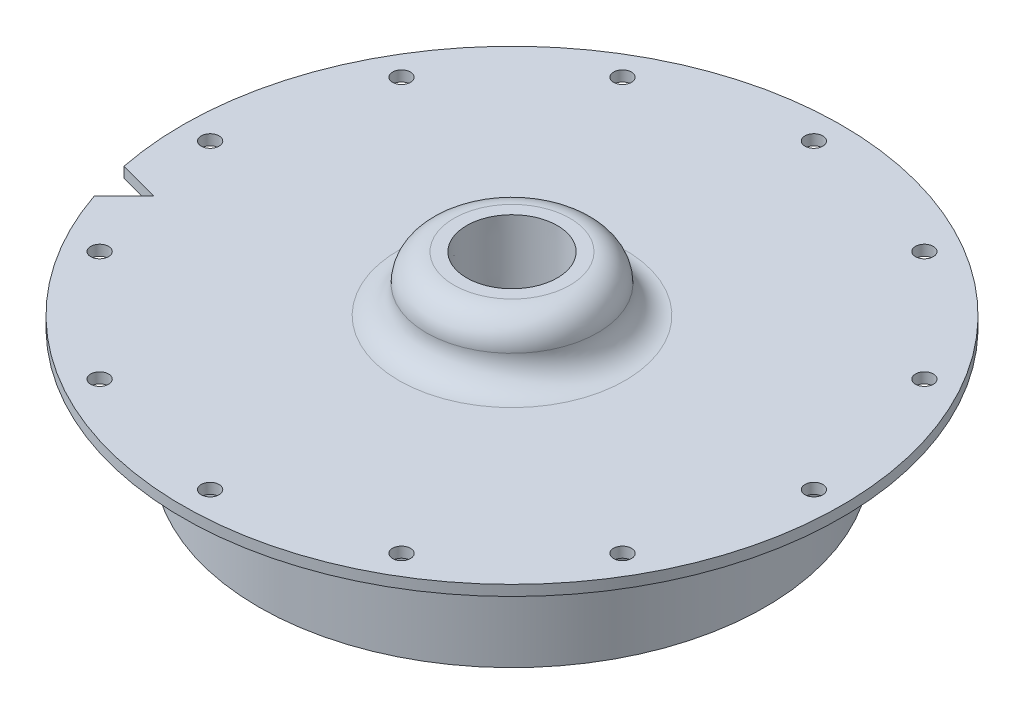
SolidWorks part; units mm, degrees
material "6063-T6"
ref_plane "Front Plane" through (0, 0, 0) normal (0, 0, 1) x (1, 0, 0)
ref_plane "Top Plane" through (0, 0, 0) normal (0, 1, 0) x (1, 0, 0)
ref_plane "Right Plane" through (0, 0, 0) normal (1, 0, 0) x (0, 0, -1)
ref_axis "Axis1" through (0, 55, 0) along (0, -1, 0)
sketch "Sketch1" plane through (0, 0, 0) normal (0, 0, 1) x (1, 0, 0)
  line L0 (-49.784, 0) -> (-39.8399, 0)
  line L1 (0, 55) -> (0, -55) construction
  line L2 (-49.784, 0) -> (-49.784, 1.5875)
  line L3 (-5.588, 9.906) -> (-8.763, 9.906)
  line L5 (-5.588, 9.906) -> (-5.588, 0)
  line L6 (-5.588, 0) -> (0, 0) construction
  line L7 (-49.784, 0) -> (-49.784, 1.5875) construction
  line L8 (-5.588, 1.5875) -> (-5.588, 0) construction
  line L9 (-38.2524, -1.5875) -> (-38.2524, -17.4625)
  line L10 (-38.2524, -17.4625) -> (-35.0774, -17.4625)
  line L11 (-35.0774, -17.4625) -> (-35.0774, -3.175)
  line L12 (-31.9024, 0) -> (-5.588, 0)
  line L13 (0, -201000) -> (0, 249000) construction
  line L14 (-49.784, 1.5875) -> (-17.0815, 1.5875)
  arc A0 (-35.0774, -3.175) -> (-31.9024, 0) centre (-31.9024, -3.175) cw
  arc A1 (-38.2524, -1.5875) -> (-39.8399, 0) centre (-39.8399, -1.5875) ccw
  arc A2 (-17.0815, 1.5875) -> (-12.9223, 5.7467) centre (-17.0815, 5.7467) ccw
  arc A3 (-8.763, 9.906) -> (-12.9223, 5.7467) centre (-8.763, 5.7467) ccw
  point P18 (-35.0774, 0)
  point P25 (0, 0)
  point P28 (-15.0934, 1.8081)
  point P29 (0, 0)
  dimension "D4" = 3.175
  dimension "D5" = 1.5875
  dimension "D1" = 3.175
  dimension "D2" = 38.2524
  dimension "D3" = 17.4625
  dimension "D6" = 1.5875
  dimension "D7" = 3.175
  dimension "D8" = 9.906
revolve "Revolve1" add sketch "Sketch1" angle 360 about axis through (0, 55, 0) along (0, -1, 0)
ref_plane "Hole Location Plane" through (0, 3.175, 0) normal (0, 1, 0) x (1, 0, 0)
sketch "Hole Location" plane through (0, 3.175, 0) normal (0, 1, 0) x (1, 0, 0)
  line L0 (0, 0) -> (-45.6057, 0) construction
  circle A0 centre (0, 0) radius 45.6057 construction
  dimension "D1" = 91.2114
hole_wizard "#36 (0.1065) Diameter Hole1" positions "Sketch2" profile "Sketch3" hole size "#36" standard "ANSI Inch" end condition through all
sketch "Sketch2" plane through (0, 1.5875, 0) normal (0, 1, 0) x (1, 0, 0)
  point P0 (-45.6057, 0)
sketch "Sketch3" plane through (-45.6057, 1.5875, 0) normal (1, 0, 0) x (0, 0, 1)
  line L0 (0, 0) -> (0, 19.05)
  line L1 (0, 19.05) -> (1.3525, 19.05)
  line L2 (1.3525, 19.05) -> (1.3525, 0)
  line L5 (1.3525, 0) -> (0, 0)
  line L11 (0, -6.35) -> (0, 107.95) construction
  dimension "Thru Hole Dia." = 2.7051
  dimension "Thru Hole Depth" = 19.05
pattern_circular "CirPattern1" count 12 over 360 of "#36 (0.1065) Diameter Hole1"
hole_wizard "1/4 NPT Tapped Hole1" positions "Sketch4" profile "Sketch5" size "1/4" standard "ANSI Inch" end condition through all
sketch "Sketch4" plane through (0, 9.906, 0) normal (0, 1, 0) x (1, 0, 0)
  point P0 (0, 0)
sketch "Sketch5" plane through (0, 9.906, 0) normal (1, 0, 0) x (0, 0, 1)
  line L0 (0, 0) -> (0, 27.3685)
  line L1 (0, 27.3685) -> (5.5626, 27.3685)
  line L2 (-6.558, 9.906) -> (-6.8546, 0) construction
  line L3 (5.5626, 27.3685) -> (5.5626, 9.906)
  line L4 (5.5626, 9.906) -> (6.558, 9.906)
  line L5 (6.558, 9.906) -> (6.8546, 0)
  line L7 (6.8546, 0) -> (0, 0)
  line L8 (0, -6.35) -> (0, 107.95) construction
  line L11 (-5.5626, 9.906) -> (-6.558, 9.906) construction
  dimension "Thru Tap Drill Dia." = 11.1252
  dimension "Thru Tap Drill Depth" = 27.3685
  dimension "Thread Dia." = 13.7092
  dimension "Thread Angle" = 3.43
  dimension "Thread Depth" = 9.906
sketch "Sketch6" plane through (0, 1.5875, 0) normal (0, 1, 0) x (1, 0, 0)
  line L0 (0, 0) -> (-48.0877, -12.885) construction
  line L1 (0, 0) -> (-45.6057, 0) construction
  line L2 (-47.168, -15.9256) -> (-42.6779, -11.4355)
  line L3 (-42.6779, -11.4355) -> (-48.8115, -9.792)
  circle A0 centre (0, 0) radius 49.784 construction
  arc A1 (-47.168, -15.9256) -> (-48.8115, -9.792) centre (0, 0) cw
  circle M16 centre (0, 0) radius 49.784
  dimension "D1" = 15
  dimension "D2" = 60
  dimension "D3" = 6.35
extrude "Cut-Extrude1" cut sketch "Sketch6" against normal up to surface (1.5875 mm away) contours L2 L0 A1 | L0 L3 M16 region at (-45.9878, 1.5875, 13.4214) region at (-46.5373, 1.5875, 11.3707) up to face at (-39.4957, 0, -24.1554)
equation "\"D1@Hole Location\"=\"TANK DIAMETER@Cryo Tank.Assembly\"+\"GASKET SEAT THICKNESS@Cryo Tank.Assembly\"+\"LINER THICKNESS@Cryo Tank.Assembly\"+\"SHRINK FIT DELTA@Cryo Tank.Assembly\""
equation "\"D2@Sketch1\"=\"TANK DIAMETER@Cryo Tank.Assembly\"/2+\"SHRINK FIT DELTA@Cryo Tank.Assembly\""
equation "\"D3@Sketch1\"=0.5+0.125+0.0625"
